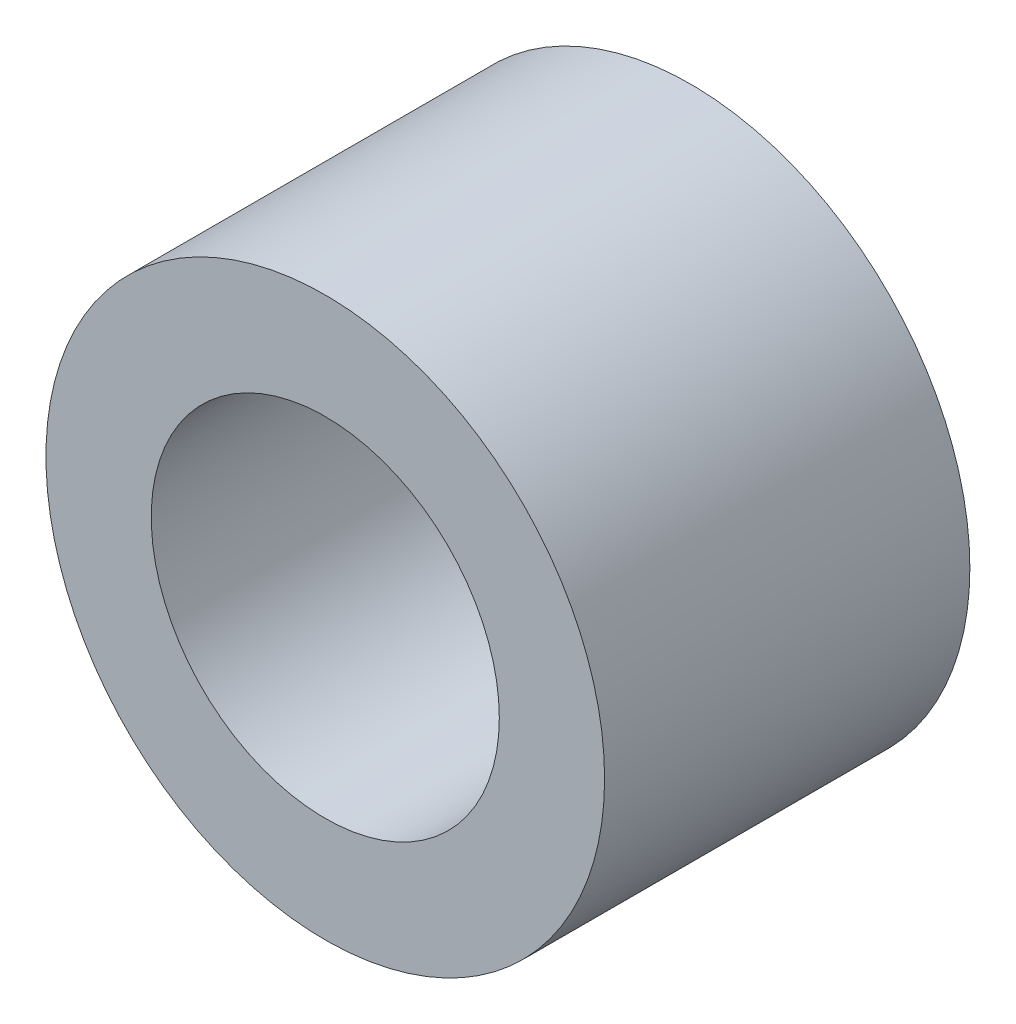
SolidWorks part; units mm, degrees
material "PETG"
ref_plane "Front Plane" through (0, 0, 0) normal (0, 0, 1) x (1, 0, 0)
ref_plane "Top Plane" through (0, 0, 0) normal (0, 1, 0) x (1, 0, 0)
ref_plane "Right Plane" through (0, 0, 0) normal (1, 0, 0) x (0, 0, -1)
sketch "Sketch1" plane through (0, 0, 0) normal (0, 0, 1) x (1, 0, 0)
  circle A0 centre (0, 0) radius 4.05
  circle A1 centre (0, 0) radius 6.5
  dimension "D1" = 8.1
  dimension "D2" = 13
extrude "Boss-Extrude1" add sketch "Sketch1" along normal mid plane 8.5
equation "\"tol_dia_id_intfc\"= 0.0500mm ' For hole diameters - Interference fit"
equation "\"tol_dia_id_slip\"= 0.0750mm ' For hole diameters - Slip fit"
equation "\"tol_dia_id_clear\"= 0.1000mm ' For hole diameters - Clearance fit"
equation "\"tol_dia_od_intfc\"= 0.0500mm ' For shaft diameters - Interference fit"
equation "\"tol_dia_od_slip\"= 0.0750mm ' For shaft diameters - Slip fit"
equation "\"tol_dia_od_clear\"= 0.1000mm ' For shaft diameters - Clearance fit"
equation "\"tol_general_intfc\"= 0.0250mm ' For general parts (Horiz) - Interference fit"
equation "\"tol_general_slip\"= 0.0375mm ' For general parts (Horiz) - Slip fit"
equation "\"tol_general_clear\"= 0.0500mm ' For general parts (Horiz) - Clearance fit"
equation "\"tol_layer_intfc\"= 0.0250mm ' For all parts (Vert) - Interference fit"
equation "\"tol_layer_slip\"= 0.0375mm ' For all parts (Vert) - Slip fit"
equation "\"tol_layer_clear\"= 0.0500mm ' For all parts (Vert) - Clearance fit"
equation "\"tol_corner_rad\"= 0.100mm ' For corners that fit into other parts"
equation "\"D1@Sketch1\"=8.00mm+\"tol_dia_id_clear\""
